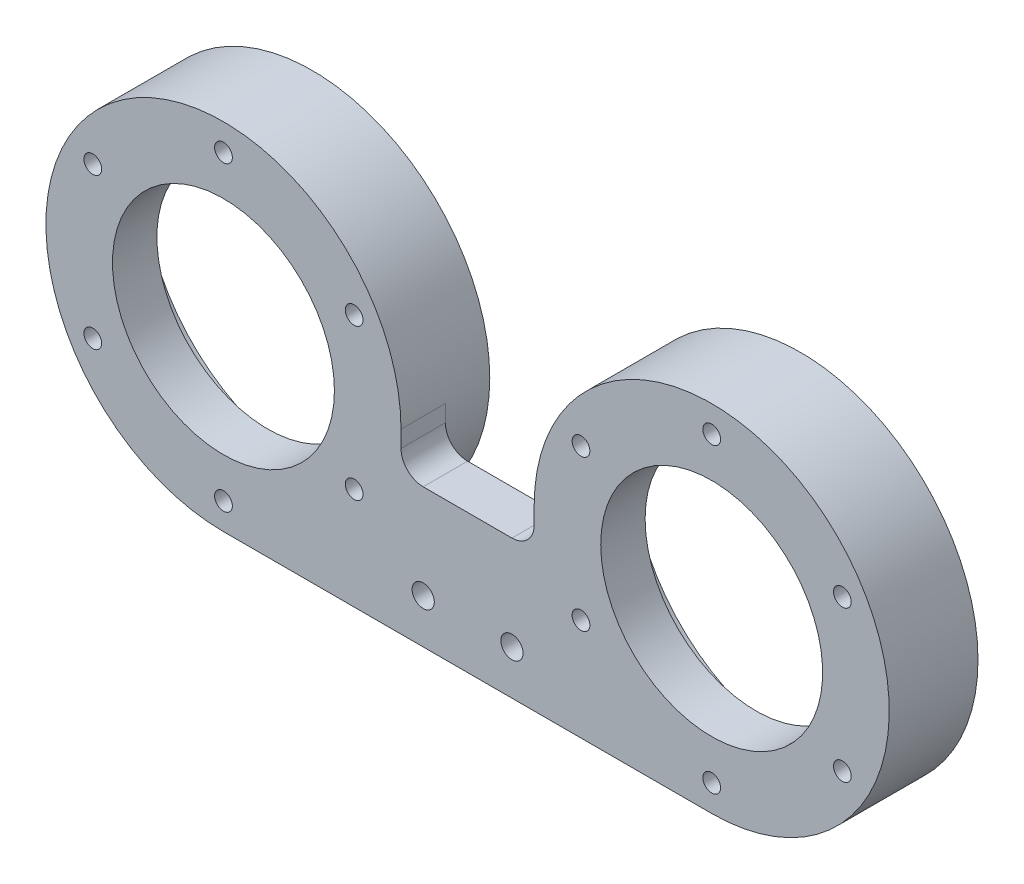
SolidWorks part; units mm, degrees
ref_plane "Front Plane" through (0, 0, 0) normal (0, 0, 1) x (1, 0, 0)
ref_plane "Top Plane" through (0, 0, 0) normal (0, 1, 0) x (1, 0, 0)
ref_plane "Right Plane" through (0, 0, 0) normal (1, 0, 0) x (0, 0, -1)
sketch "Sketch1" plane through (0, 0, 0) normal (0, 0, 1) x (1, 0, 0)
  line L0 (0, 0) -> (0, 41.85) construction
  line L2 (0, 0) -> (55, 0) construction
  line L3 (55, 0) -> (55, 40) construction
  line L4 (110, 0) -> (121.6469, 43.4667) construction
  line L5 (110, 0) -> (110, 45) construction
  line L8 (80, 40) -> (80, -40) construction
  line L12 (30, 40) -> (30, -34.2802) construction
  line L19 (0, 40) -> (110, 40)
  line L20 (110, -40) -> (0, -40)
  arc A20 (25, 0) -> (-25, 0) centre (0, 0) ccw
  arc A21 (-25, 0) -> (25, 0) centre (0, 0) ccw
  arc A58 (0, 40) -> (0, -40) centre (0, 0) ccw
  arc A59 (110, 40) -> (110, -40) centre (110, 0) cw
  arc A60 (135, 0) -> (85, 0) centre (110, 0) cw
  arc A61 (85, 0) -> (135, 0) centre (110, 0) cw
  circle A62 centre (0, 0) radius 34 construction
  circle A63 centre (0, 34) radius 2
  circle A64 centre (29.4449, 17) radius 2
  circle A65 centre (29.4449, -17) radius 2
  circle A66 centre (0, -34) radius 2
  circle A67 centre (-29.4449, -17) radius 2
  circle A68 centre (-29.4449, 17) radius 2
  circle A69 centre (110, -34) radius 2
  circle A70 centre (110, 0) radius 34 construction
  circle A71 centre (139.4449, 17) radius 2
  circle A72 centre (139.4449, -17) radius 2
  circle A73 centre (80.5551, -17) radius 2
  circle A74 centre (80.5551, 17) radius 2
  circle A75 centre (110, 34) radius 2
  circle A76 centre (45, 30) radius 2.5
  circle A77 centre (65, 30) radius 2.5
  circle A78 centre (65, -30) radius 2.5
  circle A79 centre (45, -30) radius 2.5
  point P18 (0, 0)
  point P30 (110, 0)
  point P37 (26.0991, 55.32)
  point P113 (55, -40)
  point P118 (55, -40)
  point P119 (55, -40)
  point P120 (55, -40)
  dimension "D1" = 25
  dimension "D2" = 80
  dimension "D3" = 4
  dimension "D7" = 80
  dimension "D6" = 10
  dimension "D9" = 5
  dimension "D4" = 6
  dimension "D5" = 55
  dimension "D8" = 10
extrude "Boss-Extrude1" add sketch "Sketch1" along normal mid plane 10
sketch "Sketch2" plane through (0, 0, -5) normal (0, 0, -1) x (-1, 0, 0)
  line L0 (-55, -40) -> (-55, 40) construction
  line L1 (-110, 0) -> (-110, 34) construction
  line L2 (0, 0) -> (49, 0) construction
  line L3 (0, 0) -> (0, 34) construction
  line L4 (-110, 0) -> (-159, 0) construction
  line L5 (-110, 25) -> (-110, -25) construction
  circle A5 centre (-110, 0) radius 34 construction
  circle A8 centre (-110, 34) radius 3
  circle A26 centre (-80.5551, 17) radius 3
  circle A27 centre (-80.5551, -17) radius 3
  circle A28 centre (-110, -34) radius 3
  circle A29 centre (-139.4449, -17) radius 3
  circle A30 centre (-139.4449, 17) radius 3
  circle A31 centre (0, 0) radius 34 construction
  circle A32 centre (29.4449, 17) radius 3
  circle A33 centre (29.4449, -17) radius 3
  circle A34 centre (0, -34) radius 3
  circle A35 centre (-29.4449, -17) radius 3
  circle A36 centre (-29.4449, 17) radius 3
  circle A37 centre (0, 34) radius 3
  circle A38 centre (-110, 0) radius 25 construction
  point P19 (-110, 0)
  point P34 (0, 0)
  point P35 (-110, 0)
  dimension "D1" = 68
  dimension "D2" = 6
extrude "Cut-Extrude2" cut sketch "Sketch2" against normal blind 5
ref_plane "Plane1" through (100, 0, 0) normal (1, 0, 0) x (0, 0, -1)
sketch "Sketch6" plane through (0, 0, -5) normal (0, 0, 1) x (1, 0, 0)
  line L0 (55, 40) -> (55, -40) construction
  circle A0 centre (0, 0) radius 38
  circle A1 centre (0, 0) radius 40
  circle A3 centre (110, 0) radius 40
  circle A4 centre (110, 0) radius 38
  arc A5 (0, 40) -> (0, -40) centre (0, 0) ccw construction
  point P6 (134, 0)
  dimension "D1" = 76
extrude "Boss-Extrude2" add sketch "Sketch6" against normal blind 10
sketch "Sketch7" plane through (0, 0, 5) normal (0, 0, 1) x (1, 0, 0)
  line L0 (40, 0) -> (70, 0) construction
  line L4 (110, 52.8) -> (110, 40)
  line L5 (0, 52.8) -> (110, 52.8)
  line L6 (0, 40) -> (0, 52.8)
  line L7 (40, 0) -> (40, -8.75)
  line L8 (40, -8.75) -> (70, -8.75)
  line L9 (70, -8.75) -> (70, 0)
  arc A0 (40, 0) -> (0, 40) centre (0, 0) ccw
  arc A1 (110, 40) -> (70, 0) centre (110, 0) ccw
  dimension "D1" = 17.5
extrude "Cut-Extrude3" cut sketch "Sketch7" against normal blind 29
fillet "Fillet1" radius 5 2 edges at (70, -8.75, 0) (40, -8.75, 0)
equation "\"c\"=6.25"
